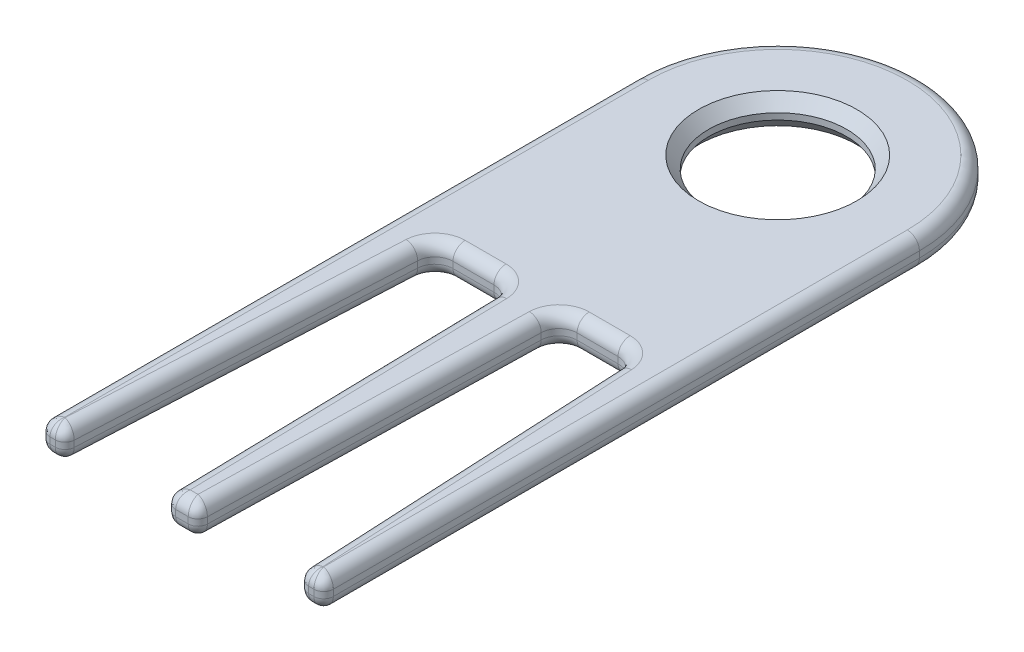
SolidWorks part; units mm, degrees
ref_plane "Front Plane" through (0, 0, 0) normal (0, 0, 1) x (1, 0, 0)
ref_plane "Top Plane" through (0, 0, 0) normal (0, 1, 0) x (1, 0, 0)
ref_plane "Right Plane" through (0, 0, 0) normal (1, 0, 0) x (0, 0, -1)
sketch "Sketch2" plane through (0, 0, 0) normal (1, 0, 0) x (0, 0, -1)
  line L2 (6.5, 3) -> (-6.5, 3) construction
  line L3 (6.5, 6.2) -> (-6.5, 6.2)
  dimension "D1" = 3.2
ref_plane "Plane1" through (0, 6.2, 0) normal (0, 1, 0) x (0, 0, 1)
sketch "Sketch3" plane through (0, 6.2, 0) normal (0, 1, 0) x (0, 0, 1)
  line L0 (-12, 0) -> (-5.3, 0)
  line L1 (49.2, 11.7) -> (49.2, 9.7)
  line L2 (49.2, 1.299) -> (49.2, 0)
  line L4 (20, 1.9661) -> (20, 8.24)
  line L5 (5.3, 0) -> (49.2, 0)
  line L11 (-12, 11.7) -> (49.2, 11.7)
  line L12 (-12, 11.7) -> (-12, 0)
  line L20 (20, 1.9661) -> (49.2, 1.299)
  line L21 (49.2, 9.7) -> (20, 8.24)
  arc A1 (5.3, 0) -> (-5.3, 0) centre (0, 0) ccw
  dimension "D1" = 11.7
  dimension "D2" = 20
extrude "Boss-Extrude1" add sketch "Sketch3" along normal blind 2.52
sketch "Sketch5" plane through (0, 6.2, 0) normal (0, 1, 0) x (0, 0, 1)
  line L0 (49.2, 11.7) -> (-12, 11.7) construction
  line L1 (0, 11.7) -> (0, 17.1392)
  line L2 (0, 17.1392) -> (-16.3974, 17.1392)
  line L3 (-16.3974, 17.1392) -> (-16.3974, -4.6342)
  line L4 (-16.3974, -4.6342) -> (-10.7431, -4.6342)
  arc A0 (0, 11.7) -> (-10.7431, -4.6342) centre (0, 0) ccw
  arc A1 (5.3, 0) -> (-5.3, 0) centre (0, 0) ccw construction
extrude "Cut-Extrude1" cut sketch "Sketch5" along normal blind 5
sketch "Sketch6" plane through (0, 6.2, 0) normal (0, 1, 0) x (0, 0, 1)
  circle A0 centre (0, 0) radius 5 construction
  arc A1 (5.3, 0) -> (-5.3, 0) centre (0, 0) ccw construction
  circle A2 centre (0, 0) radius 5.7
  dimension "D1" = 10
  dimension "D2" = 0.7
extrude "Cut-Extrude2" cut sketch "Sketch6" along normal blind 12
fillet "Fillet2" radius 1.5 2 edges at (1.9661, 7.46, 20) (8.24, 7.46, 20)
chamfer "Chamfer1" distance 1 angle 40 2 edges at (5.7, 6.2, 0) (5.7, 8.72, 0) first distance on face at (2.85, 7.46, 0)
mirror "Mirror1" about plane through (0, 0, 0) normal (1, 0, 0) of bodies 104 101
fillet "Fillet3" radius 0.8 6 edges at (-11.7, 7.46, 49.2) (-9.7, 7.46, 49.2) (-1.299, 7.46, 49.2) (1.299, 7.46, 49.2) (9.7, 7.46, 49.2) (11.7, 7.46, 49.2)
fillet "Fillet4" radius 1 40 edges at (11.4657, 8.72, 48.9657) (10.6805, 8.72, 49.2) (9.9096, 8.72, 48.9796) (8.9866, 8.72, 34.9325) (7.847, 8.72, 20.4132) (5.1227, 8.72, 20) (2.3838, 8.72, 20.4273) (1.6248, 8.72, 34.942) (1.0763, 8.72, 48.9721) (0, 8.72, 49.2) (-1.0763, 8.72, 48.9721) (-1.6248, 8.72, 34.942) (-2.3838, 8.72, 20.4273) (-5.1227, 8.72, 20) (-7.847, 8.72, 20.4132) (-8.9866, 8.72, 34.9325) (-9.9096, 8.72, 48.9796) (-10.6805, 8.72, 49.2) (-11.4657, 8.72, 48.9657) (11.4657, 6.2, 48.9657) (10.6805, 6.2, 49.2) (9.9096, 6.2, 48.9796) (8.9866, 6.2, 34.9325) (7.847, 6.2, 20.4132) (5.1227, 6.2, 20) (2.3838, 6.2, 20.4273) (1.6248, 6.2, 34.942) (1.0763, 6.2, 48.9721) (0, 6.2, 49.2) (-1.0763, 6.2, 48.9721) (-1.6248, 6.2, 34.942) (-2.3838, 6.2, 20.4273) (-5.1227, 6.2, 20) (-7.847, 6.2, 20.4132) (-8.9866, 6.2, 34.9325) (-9.9096, 6.2, 48.9796) (-10.6805, 6.2, 49.2) (-11.4657, 6.2, 48.9657) (11.7, 8.72, 24.2) (11.7, 6.2, 24.2)
